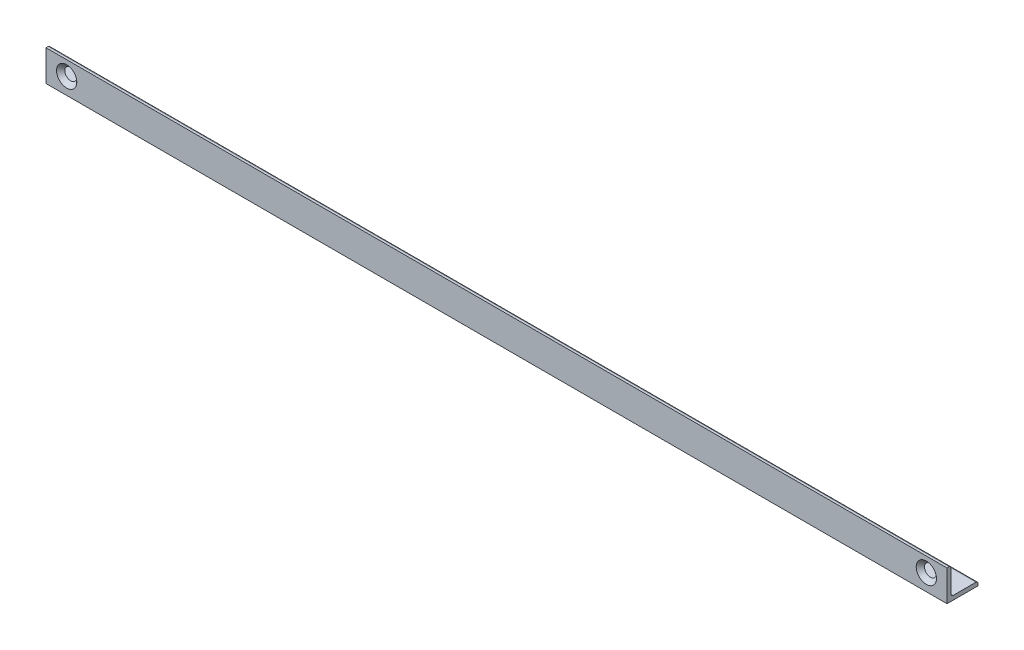
SolidWorks part; units mm, degrees
material "1060 Сплав"
ref_plane "Front" through (0, 0, 0) normal (0, 0, 1) x (1, 0, 0)
ref_plane "Top" through (0, 0, 0) normal (0, 1, 0) x (1, 0, 0)
ref_plane "Right" through (0, 0, 0) normal (1, 0, 0) x (0, 0, -1)
sketch "Эскиз1" plane through (0, 0, 0) normal (1, 0, 0) x (0, 0, -1)
  line L0 (0, 0) -> (0, 15)
  line L1 (0, 0) -> (15, 0)
  line L2 (0, 15) -> (1, 15)
  line L3 (2, 14) -> (2, 3)
  line L4 (3, 2) -> (14, 2)
  line L5 (15, 1) -> (15, 0)
  arc A0 (14, 2) -> (15, 1) centre (14, 1) cw
  arc A1 (1, 15) -> (2, 14) centre (1, 14) cw
  arc A2 (2, 3) -> (3, 2) centre (3, 3) ccw
  point P9 (15, 2)
  point P12 (2, 15)
  dimension "D5" = 1
  dimension "D1" = 15
  dimension "D2" = 15
  dimension "D3" = 2
  dimension "D4" = 2
extrude "Бобышка-Вытянуть1" add sketch "Эскиз1" along normal blind 436
sketch "Эскиз3" plane through (0, 0, -2) normal (0, 0, -1) x (-1, 0, 0)
  line L0 (-436, 3) -> (-436, 14) construction
  line L1 (-436, 15) -> (0, 15) construction
  line L2 (0, 3) -> (0, 14) construction
  circle A0 centre (-411, 8) radius 2.8
  circle A1 centre (-25, 8) radius 2.8
  dimension "D1" = 5.6
  dimension "D2" = 25
  dimension "D3" = 7
  dimension "D4" = 5.6
  dimension "D5" = 7
  dimension "D6" = 25
extrude "Вырез-Вытянуть2" [suppressed] cut sketch "Эскиз3" against normal through all
sketch "Эскиз4" plane through (0, 0, 0) normal (0, -1, 0) x (1, 0, 0)
  line L0 (436, -15) -> (0, -15) construction
  line L2 (436, 0) -> (436, -15) construction
  circle A0 centre (372, -9) radius 2.75
  circle A2 centre (90, -9) radius 2.75
  dimension "D1" = 5.5
  dimension "D2" = 6
  dimension "D3" = 64
  dimension "D4" = 5.5
  dimension "D5" = 282
  dimension "D6" = 6
extrude "Вырез-Вытянуть3" cut sketch "Эскиз4" against normal blind 2
chamfer "Фаска2" [suppressed] distance 2.098 angle 45
sketch "Эскиз5" [suppressed] plane through (0, 2, 0) normal (0, 1, 0) x (1, 0, 0)
  line L0 (436, 14) -> (436, 3) construction
  line L1 (436, 15) -> (0, 15) construction
  line L2 (0, 14) -> (0, 3) construction
  circle A0 centre (396, 8) radius 2.3
  circle A1 centre (40, 8) radius 2.3
  dimension "D1" = 4.6
  dimension "D2" = 40
  dimension "D3" = 7
  dimension "D4" = 4.6
  dimension "D5" = 7
  dimension "D6" = 40
extrude "Вырез-Вытянуть4" [suppressed] cut sketch "Эскиз5" against normal through all
chamfer "Фаска3" [suppressed] distance 2.05 angle 45
sketch "Эскиз6" [suppressed] plane through (436, 0, 0) normal (1, 0, 0) x (0, 0, -1)
  line L1 (15, 0) -> (2, 0)
  line L2 (15, 0) -> (15, 3)
  line L3 (15, 3) -> (2, 3)
  line L4 (2, 0) -> (2, 3)
extrude "Вырез-Вытянуть5" [suppressed] cut sketch "Эскиз6" against normal blind 15
sketch "Эскиз7" [suppressed] plane through (0, 0, 0) normal (-1, 0, 0) x (0, 0, 1)
  line L1 (-15, 0) -> (-2, 0)
  line L2 (-15, 0) -> (-15, 3)
  line L3 (-15, 3) -> (-2, 3)
  line L4 (-2, 0) -> (-2, 3)
extrude "Вырез-Вытянуть6" [suppressed] cut sketch "Эскиз7" against normal blind 15
sketch "Эскиз8" [suppressed] plane through (0, 0, -2) normal (0, 0, -1) x (-1, 0, 0)
  line L0 (0, 0) -> (0, 5)
  line L1 (0, 0) -> (0, 14) construction
  line L2 (0, 5) -> (-5, 0)
  line L3 (-15, 0) -> (0, 0) construction
  line L4 (-5, 0) -> (0, 0)
  line L5 (-436, 0) -> (-431, 0)
  line L6 (-421, 0) -> (-436, 0) construction
  line L7 (-436, 0) -> (-436, 5)
  line L8 (-436, 0) -> (-436, 14) construction
  line L9 (-436, 5) -> (-431, 0)
  dimension "D1" = 5
  dimension "D2" = 5
  dimension "D3" = 5
  dimension "D4" = 5
extrude "Вырез-Вытянуть7" [suppressed] cut sketch "Эскиз8" against normal through all
sketch "Эскиз9" plane through (0, 0, 0) normal (0, 0, 1) x (1, 0, 0)
  line L0 (436, 15) -> (0, 15) construction
  line L1 (436, 15) -> (436, 0) construction
  line L2 (0, 15) -> (0, 0) construction
  circle A0 centre (426, 8) radius 2.8
  circle A2 centre (10, 8) radius 2.8
  dimension "D1" = 7
  dimension "D2" = 10
  dimension "D3" = 5.6
  dimension "D4" = 7
  dimension "D5" = 10
  dimension "D6" = 5.6
extrude "Вырез-Вытянуть8" cut sketch "Эскиз9" against normal through all
chamfer "Фаска4" distance 2.098 angle 45 2 edges at (12.8, 8, 0) (428.8, 8, 0)
sketch "Эскиз10" [suppressed] plane through (0, 2, 0) normal (0, 1, 0) x (1, 0, 0)
  line L0 (436, 15) -> (0, 15) construction
  line L1 (436, 14) -> (436, 3) construction
  line L2 (0, 14) -> (0, 3) construction
  circle A0 centre (396, 8) radius 2.3
  circle A1 centre (40, 8) radius 2.3
  dimension "D1" = 4.6
  dimension "D2" = 7
  dimension "D3" = 40
  dimension "D4" = 4.6
  dimension "D5" = 7
  dimension "D6" = 40
extrude "Вырез-Вытянуть9" [suppressed] cut sketch "Эскиз10" against normal through all
chamfer "Фаска5" [suppressed] distance 2.05 angle 45
sketch "Эскиз11" [suppressed] plane through (0, 0, 0) normal (0, 0, 1) x (1, 0, 0)
  line L0 (436, 15) -> (0, 15) construction
  line L1 (376, 15) -> (272, 15)
  line L2 (376, 15) -> (376, 11)
  line L3 (376, 11) -> (272, 11)
  line L4 (272, 15) -> (272, 11)
  line L5 (436, 15) -> (436, 5) construction
  dimension "D1" = 4
  dimension "D2" = 70
  dimension "D3" = 104
extrude "Вырез-Вытянуть10" [suppressed] cut sketch "Эскиз11" against normal through all
sketch "Эскиз12" [suppressed] plane through (0, 0, -2) normal (0, 0, -1) x (-1, 0, 0)
  line L0 (-436, 15) -> (-376, 15) construction
  line L1 (-436, 5) -> (-436, 14) construction
  line L2 (-272, 15) -> (0, 15) construction
  line L3 (0, 5) -> (0, 14) construction
  circle A0 centre (-384, 8) radius 3
  circle A1 centre (-52, 8) radius 3
  dimension "D1" = 6
  dimension "D2" = 7
  dimension "D3" = 52
  dimension "D4" = 6
  dimension "D5" = 7
  dimension "D6" = 52
extrude "Вырез-Вытянуть11" [suppressed] cut sketch "Эскиз12" against normal through all
sketch "Эскиз13" [suppressed] plane through (0, 0, -2) normal (0, 0, -1) x (-1, 0, 0)
  line L0 (-436, 15) -> (0, 15) construction
  line L1 (0, 3) -> (0, 14) construction
  line L2 (-436, 3) -> (-436, 14) construction
  circle A0 centre (-52, 8) radius 3
  circle A2 centre (-384, 8) radius 3
  dimension "D1" = 6
  dimension "D2" = 7
  dimension "D3" = 52
  dimension "D4" = 6
  dimension "D5" = 7
  dimension "D6" = 52
extrude "Вырез-Вытянуть12" [suppressed] cut sketch "Эскиз13" against normal through all
sketch "Эскиз14" [suppressed] plane through (0, 2, 0) normal (0, 1, 0) x (1, 0, 0)
  line L0 (436, 14) -> (436, 3) construction
  line L1 (436, 15) -> (0, 15) construction
  line L2 (218, 14) -> (218, -35.1654) construction
  line L3 (436, 14) -> (0, 14) construction
  circle A0 centre (428, 8) radius 2.3
  circle A1 centre (8, 8) radius 2.3
  dimension "D1" = 4.6
  dimension "D2" = 8
  dimension "D3" = 7
extrude "Вырез-Вытянуть13" [suppressed] cut sketch "Эскиз14" against normal through all
chamfer "Фаска6" [suppressed] distance 2.05 angle 45
